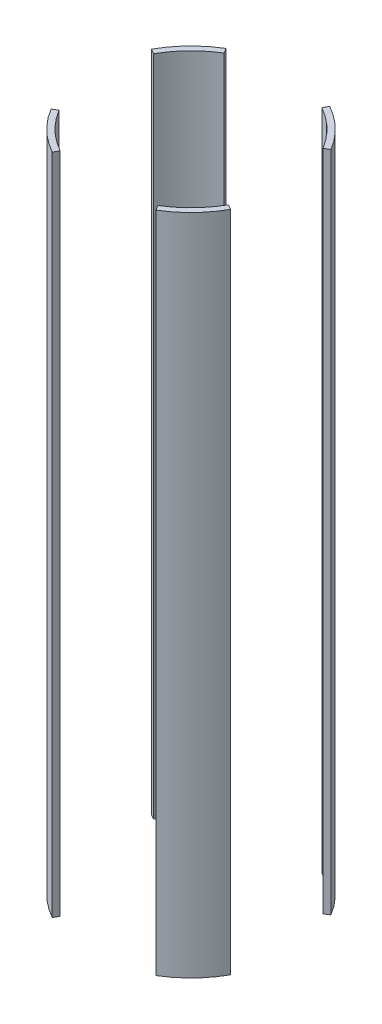
SolidWorks part; units mm, degrees
material "6061-T6 (SS)"
ref_plane "Front Plane" through (0, 0, 0) normal (0, 0, 1) x (1, 0, 0)
ref_plane "Top Plane" through (0, 0, 0) normal (0, 1, 0) x (1, 0, 0)
ref_plane "Right Plane" through (0, 0, 0) normal (1, 0, 0) x (0, 0, -1)
sketch "Sketch2" plane through (0, 0, 0) normal (0, 1, 0) x (1, 0, 0)
  circle A0 centre (0, 0) radius 88.9
  circle A1 centre (0, 0) radius 83.82
  dimension "D1" = 177.8
  dimension "D2" = 167.64
extrude "Boss-Extrude1" add sketch "Sketch2" along normal mid plane 577.596
sketch "Sketch3" plane through (0, 0, 0) normal (0, 1, 0) x (1, 0, 0)
  line L0 (0, 0) -> (169.6618, 101.6776)
  line L1 (-58.1167, 96.9749) -> (0, 0)
  line L2 (0, 0) -> (53.9, 96.9749)
  line L3 (53.9, 96.9749) -> (-58.1167, 96.9749)
  line L4 (0, 0) -> (70.9917, -118.4586)
  line L5 (70.9917, -118.4586) -> (-65.8409, -118.4586)
  line L6 (-65.8409, -118.4586) -> (0, 0)
  line L7 (169.6618, 101.6776) -> (169.6618, -94.3004)
  line L8 (169.6618, -94.3004) -> (0, 0)
  line L9 (0, 0) -> (-123.7413, 68.7771)
  line L10 (-123.7413, 68.7771) -> (-123.7413, -74.1577)
  line L11 (-123.7413, -74.1577) -> (0, 0)
  dimension "D1" = 60
  dimension "D2" = 60
  dimension "D3" = 60
  dimension "D4" = 60
  dimension "D5" = 30
  dimension "D6" = 30
extrude "Cut-Extrude1" cut sketch "Sketch3" against normal through all both and the other way through all contours L8 L7 L0 | L2 L3 L1 | L10 L11 L9 | L6 L5 L4 region at (-1.4056, 0, -64.65) region at (1.7169, 0, 78.9724) region at (113.1078, 0, -2.4591) region at (-82.4942, 0, 1.7935)
equation "\"D1@Boss-Extrude1\"=3*12"
